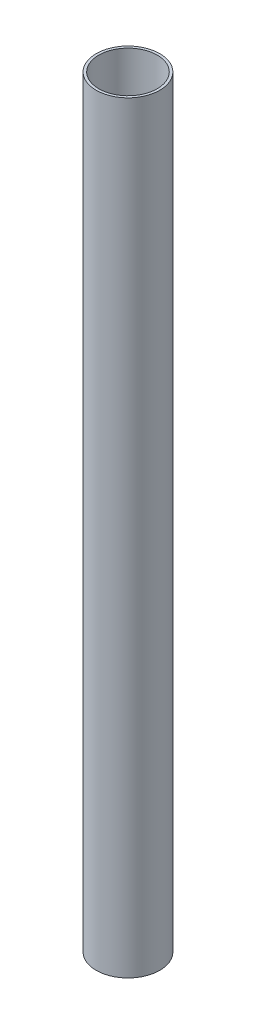
SolidWorks part; units mm, degrees
ref_plane "Front Plane" through (0, 0, 0) normal (0, 0, 1) x (1, 0, 0)
ref_plane "Top Plane" through (0, 0, 0) normal (0, 1, 0) x (1, 0, 0)
ref_plane "Right Plane" through (0, 0, 0) normal (1, 0, 0) x (0, 0, -1)
sketch "Sketch1" plane through (0, 0, 0) normal (0, 1, 0) x (1, 0, 0)
  circle A0 centre (0, 0) radius 1.25
  dimension "D1" = 2.5
extrude "Boss-Extrude1" add sketch "Sketch1" along normal blind 30
sketch "Sketch2" plane through (0, 30, 0) normal (0, 1, 0) x (1, 0, 0)
  circle A0 centre (0, 0) radius 1.15
  dimension "D1" = 2.3
extrude "Cut-Extrude1" cut sketch "Sketch2" against normal through all
